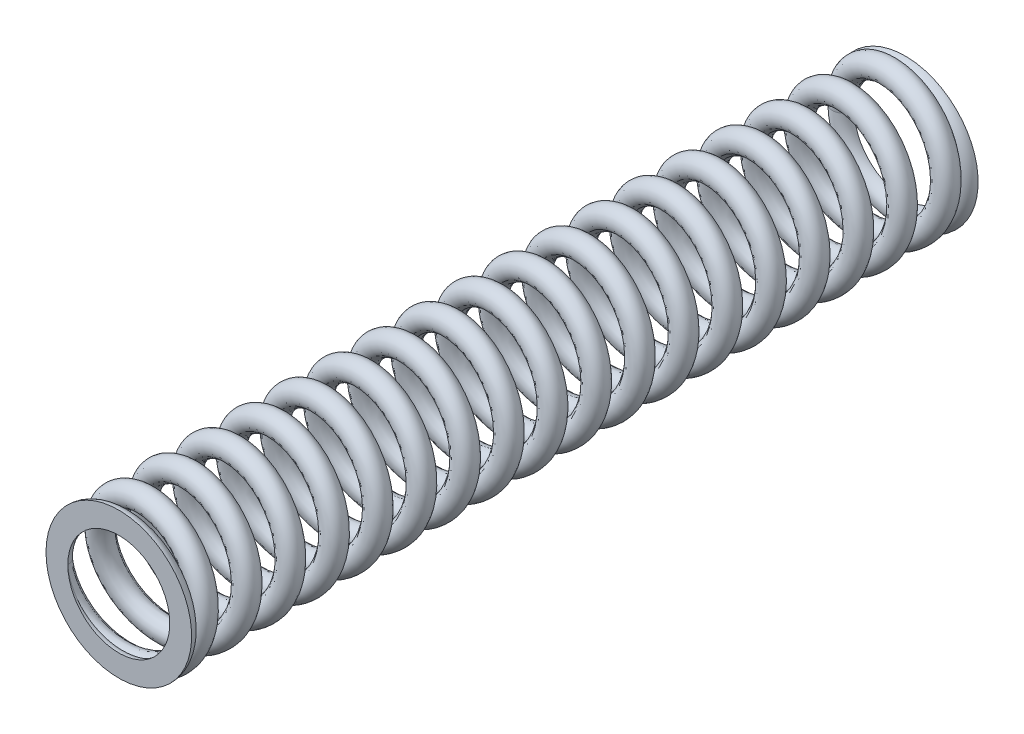
SolidWorks part; units mm, degrees
note: The reader was unsure of these and kept them because the rebuilt part matched: shared geometry of "Sketch2<4>", "Sketch2<5>".
material "Alloy Steel"
ref_plane "Front Plane" through (0, 0, 0) normal (0, 0, 1) x (1, 0, 0)
ref_plane "Top Plane" through (0, 0, 0) normal (0, 1, 0) x (1, 0, 0)
ref_plane "Right Plane" through (0, 0, 0) normal (1, 0, 0) x (0, 0, -1)
sketch "Sketch1" plane through (0, 0, 0) normal (0, 0, 1) x (1, 0, 0)
  circle A0 centre (0, 0) radius 4.25
  dimension "D1" = 8.5
curve "Helix/Spiral1" pitch 3 height 54 turns 18
sketch "Sketch2" plane through (0, 0, 0) normal (0, 1, 0) x (1, 0, 0)
  line L0 (-5, -54) -> (-3.5, -54)
  line L1 (-5, 0) -> (-3.5, 0)
  line L2 (0, 0) -> (0, -8.673) construction
  circle A0 centre (-4.25, 0) radius 0.75
  circle A1 centre (-4.25, -54) radius 0.75
  dimension "D1" = 1.5
  dimension "D2" = 1.5
sweep "Sweep1" add profiles "Sketch2" path "Helix/Spiral1"
revolve "Revolve1" add sketch "Sketch2<4>" angle 360 about L2
sketch "Sketch2<4>" plane through (0, 0, 0) normal (0, 1, 0) x (1, 0, 0) same geometry as "Sketch2"
revolve "Cut-Revolve1" cut sketch "Sketch2<5>" angle 360 about L2
sketch "Sketch2<5>" plane through (0, 0, 0) normal (0, 1, 0) x (1, 0, 0) same geometry as "Sketch2"
equation "\"C\"= 54mm"
equation "\"D3@Helix/Spiral1\"=\"C\""
equation "\"NC\"= 64mm"
